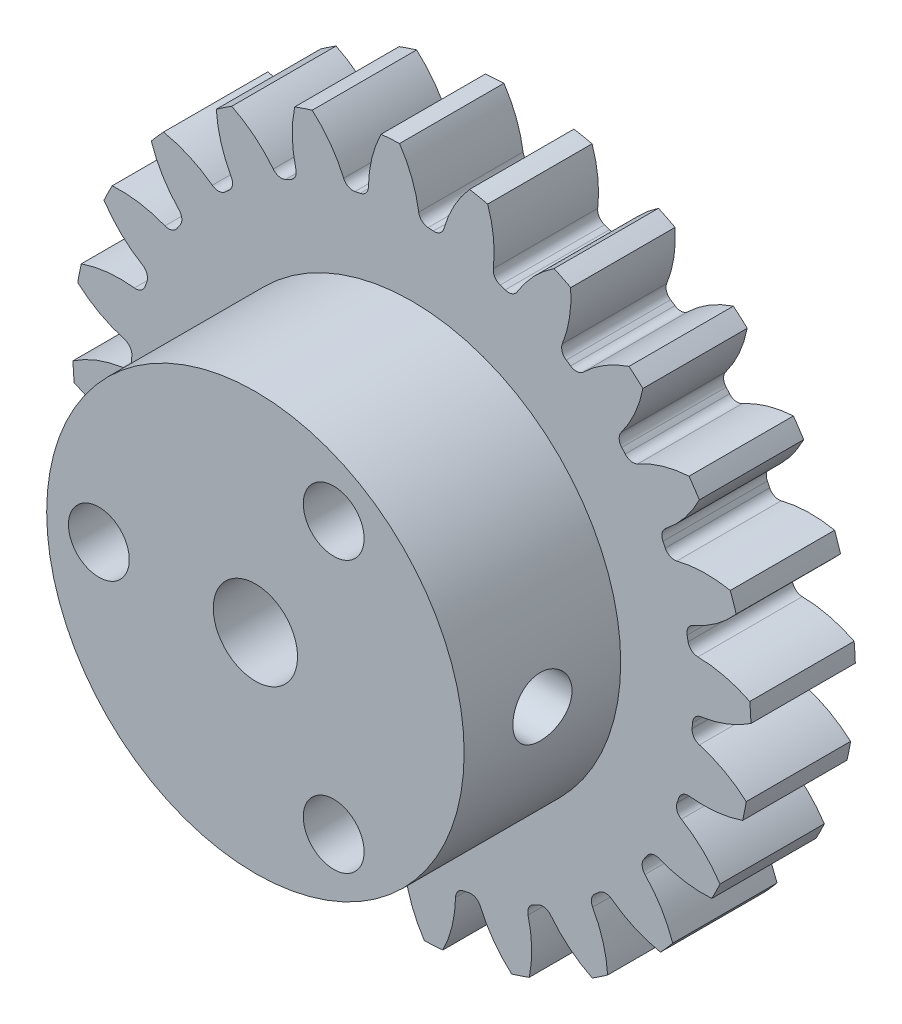
SolidWorks part; units mm, degrees
ref_plane "Front" through (0, 0, 0) normal (0, 0, 1) x (1, 0, 0)
ref_plane "Top" through (0, 0, 0) normal (0, 1, 0) x (1, 0, 0)
ref_plane "Right" through (0, 0, 0) normal (1, 0, 0) x (0, 0, -1)
sketch "Sketch3" plane through (0, 0, 0) normal (0, 0, 1) x (1, 0, 0)
  circle A0 centre (0, 0) radius 20.6375
  dimension "od" = 41.275
extrude "gearBody" add sketch "Sketch3" along normal blind 6.35
sketch "Sketch2" plane through (0, 0, 0) normal (0, 0, 1) x (1, 0, 0)
  line L0 (0, 0) -> (16.5385, 6.8505) construction
  line L1 (22.0347, -5.709) -> (0, 0) construction
  line L2 (0, 0) -> (36.3143, 0) construction
  line L3 (19.05, -0.043) -> (18.8852, -2.5004) construction
  line L5 (18.9676, -1.2717) -> (0, 0) construction
  line L7 (0, 0) -> (17.9011, 0) construction
  arc A0 (17.8975, -0.3593) -> (17.7853, -2.0332) centre (0, 0) ccw construction
  arc A1 (20.6236, 0.7563) -> (20.3381, -3.5027) centre (0, 0) ccw construction
  arc A2 (19.05, -0.043) -> (18.8852, -2.5004) centre (0, 0) ccw construction
  arc A3 (17.0444, -1.304) -> (17.0659, -0.983) centre (0, 0) ccw
  arc A4 (22.0347, -5.709) -> (17.4884, -1.9416) centre (15.476, -8.9969) ccw
  arc A5 (22.0347, -5.709) -> (22.5996, 2.7164) centre (0, 0) ccw
  arc A6 (22.5996, 2.7164) -> (17.5911, -0.4103) centre (16.5385, 6.8505) cw
  arc A7 (17.0659, -0.983) -> (17.5911, -0.4103) centre (17.6793, -1.0183) cw
  arc A8 (17.4884, -1.9416) -> (17.0444, -1.304) centre (17.657, -1.3509) cw
  point P6 (22.5996, 2.7164)
  point P22 (22.0347, -5.709)
  dimension "baseDia" = 35.8023
  dimension "od" = 41.275
  dimension "pd" = 38.1
  dimension "rd" = 34.1884
  dimension "rFillet" = 0.6144
  dimension "pointX" = 22.5996
  dimension "pointY" = 2.7164
  dimension "CTT" = 2.4574
  dimension "flankCenterAngle" = 22.5
extrude "toothCut" cut sketch "Sketch2" along normal through all
pattern_circular "CirPattern1" count 24 over 360 about axis through (0, 0, 6.35) along (0, 0, -1) of "toothCut"
sketch "hub1Dia" plane through (0, 0, 0) normal (0, 0, -1) x (-1, 0, 0)
  circle A0 centre (0, 0) radius 12.7
  dimension "hub1Dia" = 25.4
sketch "hub2Dia" plane through (0, 0, 6.35) normal (0, 0, 1) x (1, 0, 0)
  circle A0 centre (0, 0) radius 12.7
  dimension "hub2dia" = 25.4
sketch "boreDia" plane through (0, 0, 0) normal (0, 0, 1) x (1, 0, 0)
  circle A0 centre (0, 0) radius 6.35
  dimension "boreDia" = 12.7
extrude "Boss-Extrude1" add sketch "hub2Dia" along normal blind 9.525
sketch "Sketch4" plane through (0, 0, 0) normal (0, 0, -1) x (-1, 0, 0)
  circle A0 centre (9.525, 0) radius 1.85
  circle A1 centre (-4.7625, -8.2489) radius 1.85
  circle A2 centre (-4.7625, 8.2489) radius 1.85
  point P9 (0, 0)
  dimension "D2" = 3.7
  dimension "D1" = 9.525
  dimension "D3" = 3
extrude "Cut-Extrude1" cut sketch "Sketch4" against normal through all
sketch "Sketch5" plane through (0, 0, 0) normal (0, 0, -1) x (-1, 0, 0)
  circle A0 centre (0, 0) radius 2.5635
  dimension "D1" = 5.127
extrude "Cut-Extrude2" cut sketch "Sketch5" against normal through all
sketch "Sketch6" plane through (0, 0, 0) normal (1, 0, 0) x (0, 0, -1)
  line L0 (-15.875, 12.7) -> (-15.875, -12.7) construction
  circle A0 centre (-11.1125, 0) radius 1.8
  dimension "D2" = 3.6
  dimension "D1" = 4.7625
extrude "Cut-Extrude3" cut sketch "Sketch6" along normal through all
equation "\"D2@Sketch4\"=3.7mm"
equation "\"D1@Sketch5\"=\"tightTol\" + 5mm"
equation "\"tightTol\" = 0.005in"
equation "\"normTol\"= 0.01in"
equation "\"looseTol\"= 0.02in"
equation "\"D2@Sketch6\"=3.6mm"
